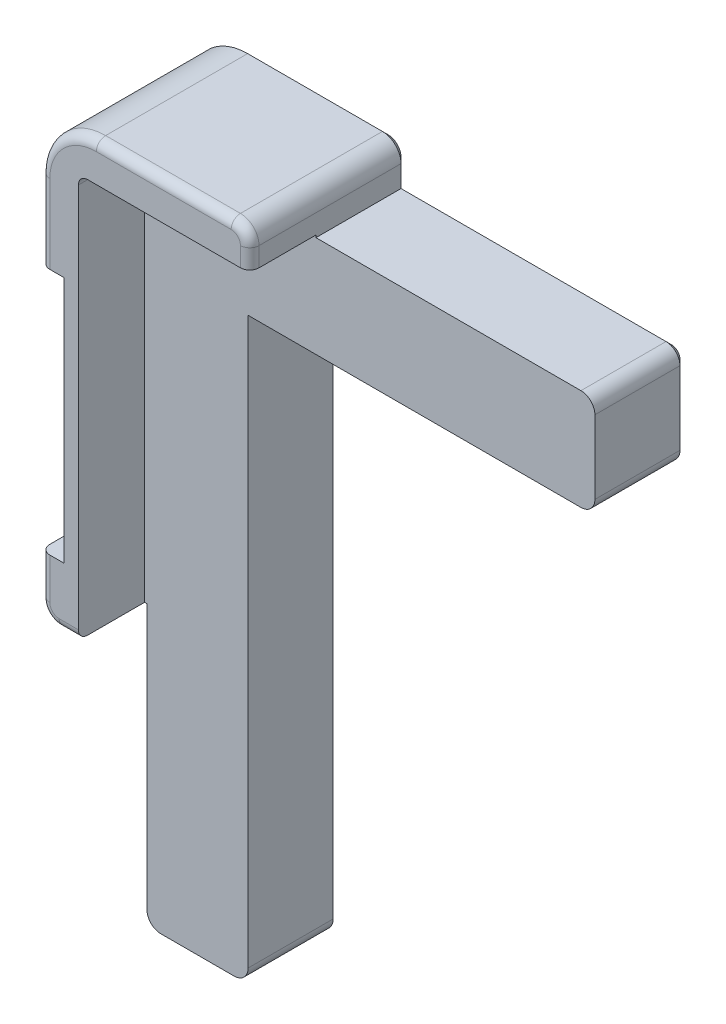
SolidWorks part; units mm, degrees
ref_plane "Front Plane" through (0, 0, 0) normal (0, 0, 1) x (1, 0, 0)
ref_plane "Top Plane" through (0, 0, 0) normal (0, 1, 0) x (1, 0, 0)
ref_plane "Right Plane" through (0, 0, 0) normal (1, 0, 0) x (0, 0, -1)
ref_plane "PZ 20.375" through (0, 0, 20.375) normal (0, 0, 1) x (1, 0, 0)
sketch "body and tongues sketch" plane through (0, 0, 20.375) normal (0, 0, 1) x (1, 0, 0)
  line L0 (-4.42, 7.07) -> (18.08, 7.07)
  line L1 (18.08, 7.07) -> (18.08, 2.75)
  line L2 (18.08, 2.75) -> (48.08, 2.75)
  line L3 (48.08, 2.75) -> (48.08, -8.13)
  line L4 (48.08, -8.13) -> (10.78, -8.13)
  line L5 (10.78, -8.13) -> (10.78, -70.43)
  line L6 (10.78, -70.43) -> (-0.1, -70.43)
  line L7 (-0.1, -70.43) -> (-0.1, -40.43)
  line L8 (-0.1, -40.43) -> (-4.42, -40.43)
  line L9 (-4.42, -40.43) -> (-4.42, 7.07)
extrude "body and tongues" add sketch "body and tongues sketch" along normal mid plane 9.75
ref_plane "PZ 23.935" through (0, 0, 23.935) normal (0, 0, 1) x (1, 0, 0)
sketch "rim sketch" plane through (0, 0, 23.935) normal (0, 0, 1) x (1, 0, 0)
  line L0 (-4.42, 7.07) -> (18.08, 7.07)
  line L1 (18.08, 7.07) -> (18.08, 3)
  line L2 (18.08, 3) -> (-0.35, 3)
  line L3 (-0.35, 3) -> (-0.35, -40.43)
  line L4 (-0.35, -40.43) -> (-4.42, -40.43)
  line L5 (-4.42, -40.43) -> (-4.42, 7.07)
extrude "rim" add sketch "rim sketch" along normal mid plane 16.87
sketch "bracket seat sketch" plane through (0, 0, 23.935) normal (0, 0, 1) x (1, 0, 0)
  line L0 (-1.92, -34) -> (-5.42, -34)
  line L1 (-5.42, -34) -> (-5.42, -7.4)
  line L2 (-5.42, -7.4) -> (-1.92, -7.4)
  line L3 (-1.92, -7.4) -> (-1.92, -34)
extrude "bracket seat" cut sketch "bracket seat sketch" against normal mid plane 18.87
ref_plane "PX 2.580" through (2.58, 0, 0) normal (1, 0, 0) x (0, 0, -1)
sketch "screw pilots sketch" plane through (2.58, 0, 0) normal (1, 0, 0) x (0, 0, -1)
  circle A0 centre (-20.375, -28.7) radius 1.35
  circle A1 centre (-20.375, -12.7) radius 1.35
extrude "screw pilots" cut sketch "screw pilots sketch" against normal mid plane 11
fillet "bumper corner" radius 6 1 edges at (-4.42, 7.07, 23.935) tangent propagation no
fillet "inside corner of the rim" radius 1 1 edges at (-0.35, 3, 28.81) tangent propagation no
fillet "rim ends" radius 2 2 edges at (18.08, 7.07, 23.935) (-4.42, -40.43, 23.935) tangent propagation no
fillet "tongue lead-in" radius 1.5 4 edges at (48.08, -8.13, 20.375) (48.08, 2.75, 20.375) (10.78, -70.43, 20.375) (-0.1, -70.43, 20.375) tangent propagation no
fillet "rim top edge" radius 1 8 edges at (18.08, 4.035, 32.37) (17.4942, 6.4842, 32.37) (-4.42, -3.165, 32.37) (-2.6626, 5.3126, 32.37) (-1.385, -40.43, 32.37) (-3.8342, -39.8442, 32.37) (8.83, 7.07, 32.37) (-4.42, -36.215, 32.37)
chamfer "bed face chamfer" distance 0.6 angle 45 21 edges at (47.6407, 2.3107, 15.5) (32.33, 2.75, 15.5) (18.08, 3.91, 15.5) (17.4942, 6.4842, 15.5) (8.83, 7.07, 15.5) (-2.6626, 5.3126, 15.5) (-4.42, -3.165, 15.5) (-3.17, -7.4, 15.5) (-1.92, -20.7, 15.5) (-3.17, -34, 15.5) (-4.42, -36.215, 15.5) (-3.8342, -39.8442, 15.5) (-1.26, -40.43, 15.5) (-0.1, -54.68, 15.5) (0.3393, -69.9907, 15.5) (5.34, -70.43, 15.5) (10.3407, -69.9907, 15.5) (10.78, -38.53, 15.5) (28.68, -8.13, 15.5) (47.6407, -7.6907, 15.5) (48.08, -2.69, 15.5)
equation "\"diffL\" = 608.8mm"
equation "\"diffW\" = 329.4mm"
equation "\"diffT\" = 2.9mm"
equation "\"chanSlotW\" = 12.9mm"
equation "\"chanSlotDepth\" = 11.13mm"
equation "\"chanFloor\" = 1.57mm"
equation "\"chanLeg\" = 12.7mm"
equation "\"lightL\" = 605mm"
equation "\"lightW\" = 331mm"
equation "\"lightH\" = 92mm"
equation "\"lightSideFlat\" = 30mm"
equation "\"lightSlopeLen\" = 33.1mm"
equation "\"lightWingDepth\" = 47.9mm"
equation "\"lightWingFlat\" = 90.2mm"
equation "\"lightChanW\" = 99.6mm"
equation "\"lightChanStand\" = 44.1mm"
equation "\"insFlangeD\" = 12.3mm"
equation "\"insFromEnd\" = 20.7mm"
equation "\"insUpSlope\" = 20.8mm"
equation "\"gaugeH\" = 10mm"
equation "\"gaugeStepLen\" = 14mm"
equation "\"gaugeStepW0\" = 13.1mm"
equation "\"gaugeStepDW\" = 0.2mm"
equation "\"gaugeSteps\" = 5mm"
equation "\"gaugeHandleLen\" = 30mm"
equation "\"gaugeHandleW\" = 24mm"
equation "\"gaugeSlot0\" = 3mm"
equation "\"gaugeSlotD\" = 0.1mm"
equation "\"gaugeSlotDepth\" = 8mm"
equation "\"gap\" = 25.4mm"
equation "\"edgeL\" = 1mm"
equation "\"edgeW\" = 0.75mm"
equation "\"proud\" = 1.5mm"
equation "\"seatClr\" = 0.15mm"
equation "\"tongueClrZ\" = 0.1mm"
equation "\"tongueClrX\" = 0.25mm"
equation "\"tongueLen\" = 30mm"
equation "\"armSide\" = 45mm"
equation "\"armEnd\" = 20mm"
equation "\"cornerCham\" = 3mm"
equation "\"brkW\" = 26mm"
equation "\"brkT\" = 7mm"
equation "\"brkSeatClr\" = 0.2mm"
equation "\"brkScrewSpan\" = 16mm"
equation "\"pilotD\" = 2.7mm"
equation "\"pilotDepth\" = 10mm"
equation "\"screwClrD\" = 3.9mm"
equation "\"jogBelow\" = 4mm"
equation "\"padT\" = 7mm"
equation "\"padLen\" = 31mm"
equation "\"m6Clr\" = 7mm"
equation "\"m6Slot\" = 3mm"
equation "\"flangeRelD\" = 17mm"
equation "\"flangeRelDepth\" = 1.5mm"
equation "\"relLen\" = 7mm"
equation "\"relDepth\" = 4mm"
equation "\"relLand\" = 2mm"
equation "\"knockN\" = 100mm"
equation "\"petgcfE\" = 3000mm"
equation "\"mockExtent\" = 110mm"
equation "\"relZnear\" = 9.4mm"
equation "\"relZfar\" = 23.4mm"
equation "\"headD\" = 8mm"
equation "\"headH\" = 2.5mm"
equation "\"headFromEnd\" = 6.8mm"
equation "\"headBack\" = 16.4mm"
equation "\"sideClr\" = 0.4mm"
equation "\"cornerRelR\" = 1.5mm"
equation "\"cornerRelBack\" = 0.6mm"
equation "\"endHeadH\" = 2.8mm"
equation "\"footClr\" = 1.2mm"
equation "\"footEndClr\" = 3.5mm"
equation "\"footLift\" = 6mm"
equation "\"footBlockClr\" = 0.5mm"
equation "\"footBack\" = 50mm"
equation "\"footFwd\" = 10mm"
equation "\"footBraceEnd\" = 3mm"
equation "\"footLoadN\" = 25mm"
equation "\"spacerLen\" = 60mm"
equation "\"spacerShort\" = 0.5mm"
equation "\"spacerCham\" = 0.8mm"
equation "\"spacerPerSide\" = 3mm"
equation "\"spacerPerEnd\" = 1mm"
equation "\"toolR\" = 9mm"
equation "\"visR\" = 4mm"
equation "\"edgeR\" = 1mm"
equation "\"bendOutR\" = 5mm"
equation "\"insideR\" = 2.5mm"
equation "\"footCornerR\" = 10mm"
equation "\"footFrontR\" = 8mm"
equation "\"braceKinkR\" = 12mm"
equation "\"bedCham\" = 1mm"
equation "\"bedChamSmall\" = 0.6mm"
equation "\"soleTopR\" = 2mm"
equation "\"cornerR\" = 6mm"
equation "\"rimInR\" = 1mm"
equation "\"insFlangeH\" = 1mm"
